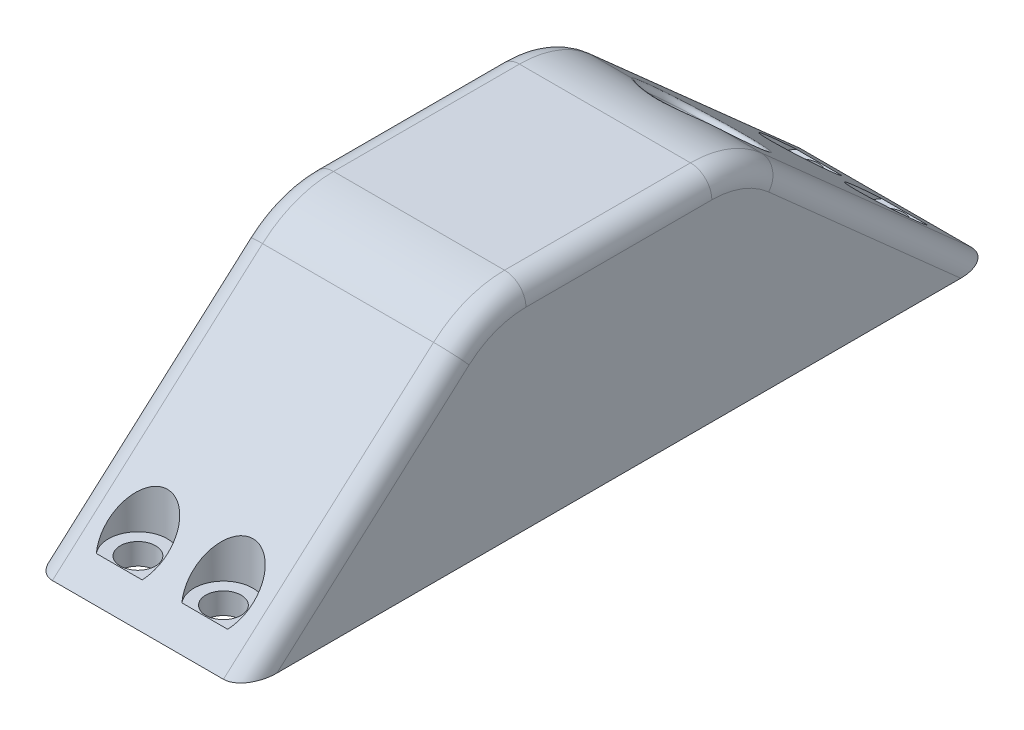
SolidWorks part; units mm, degrees
ref_plane "Front Plane" through (0, 0, 0) normal (0, 0, 1) x (1, 0, 0)
ref_plane "Top Plane" through (0, 0, 0) normal (0, 1, 0) x (1, 0, 0)
ref_plane "Right Plane" through (0, 0, 0) normal (1, 0, 0) x (0, 0, -1)
sketch "Sketch1" plane through (0, 0, 0) normal (0, 1, 0) x (1, 0, 0)
  line L0 (-14.05, 27.5) -> (14.05, 27.5)
  line L1 (-14.05, 27.5) -> (-14.05, -27.5)
  line L2 (14.05, 27.5) -> (14.05, -27.5)
  line L3 (-14.05, -27.5) -> (14.05, -27.5)
  line L4 (-14.05, 27.5) -> (14.05, -27.5) construction
  line L5 (14.05, 27.5) -> (-14.05, -27.5) construction
  point P1 (0, 0)
  dimension "D1" = 28.1
  dimension "D2" = 55
ref_plane "Plane1" through (0, 20, 0) normal (0, 1, 0) x (1, 0, 0)
sketch "Sketch2" plane through (0, 0, 0) normal (1, 0, 0) x (0, 0, -1)
  line L0 (-35, 0) -> (35, 0)
  line L1 (0, 0) -> (0, 20) construction
  line L2 (15.455, 20) -> (-15.455, 20) construction
  line L3 (-8.698, 20) -> (8.698, 20)
  line L4 (-35, 0) -> (-15.3416, 17.4741)
  line L5 (15.3416, 17.4741) -> (35, 0)
  arc A0 (8.698, 20) -> (15.3416, 17.4741) centre (8.698, 10) cw
  arc A1 (-8.698, 20) -> (-15.3416, 17.4741) centre (-8.698, 10) ccw
  point P4 (0, 0)
  point P12 (0, 20)
  point P14 (12.5, 20)
  point P17 (-12.5, 20)
  dimension "D3" = 10
  dimension "D1" = 70
  dimension "D2" = 25
extrude "Boss-Extrude1" add sketch "Sketch2" along normal blind 20
fillet "Fillet1" radius 2 10 edges at (20, 8.737, -25.1708) (20, 19.3472, -12.2518) (20, 8.737, 25.1708) (20, 19.3472, 12.2518) (20, 20, 0) (0, 8.737, -25.1708) (0, 19.3472, -12.2518) (0, 20, 0) (0, 19.3472, 12.2518) (0, 8.737, 25.1708)
ref_plane "Plane2" through (0, -17.3793, -19.5517) normal (0, -0.6644, -0.7474) x (-1, 0, 0)
sketch "Sketch3" plane through (0, -17.3793, -19.5517) normal (0, -0.6644, -0.7474) x (-1, 0, 0)
  line L0 (-18, 23.2527) -> (-2, 23.2527) construction
  line L1 (-17.05, 10.2527) -> (-2.95, 10.2527)
  line L2 (-17.05, 10.2527) -> (-17.05, -9.2473)
  line L3 (-17.05, -9.2473) -> (-2.95, -9.2473)
  line L4 (-2.95, 10.2527) -> (-2.95, -9.2473)
  line L5 (-20, -21.2527) -> (-20, 21.2527) construction
  line L7 (0, -21.2527) -> (0, 21.2527) construction
  dimension "D1" = 2.95
  dimension "D2" = 19.5
  dimension "D3" = 13
  dimension "D4" = 2.95
extrude "Cut-Extrude1" cut sketch "Sketch3" against normal blind 34 contours L2 L1 L4 L3
sketch "Sketch4" plane through (0, 7.663, -6.8115) normal (0, -0.7474, 0.6644) x (1, 0, 0)
  line L0 (2.95, 7.8407) -> (2.95, -11.5343) construction
  line L1 (2.95, 5.4657) -> (17.05, 5.4657)
  line L2 (2.95, 5.4657) -> (2.95, -11.5343)
  line L3 (2.95, -11.5343) -> (17.05, -11.5343)
  line L4 (17.05, 5.4657) -> (17.05, -11.5343)
  line L5 (17.05, 7.8407) -> (17.05, -11.5343) construction
  line L7 (10, 5.4657) -> (10, -11.5343) construction
  line L8 (2.95, -3.0343) -> (17.05, -3.0343) construction
  line L9 (2.95, -11.5343) -> (17.05, -11.5343) construction
  line L10 (2.95, -9.5343) -> (17.05, -9.5343)
  line L11 (2.95, -9.5343) -> (2.95, 3.4657)
  line L12 (2.95, 3.4657) -> (17.05, 3.4657)
  line L13 (17.05, -9.5343) -> (17.05, 3.4657)
  line L14 (2.95, -9.5343) -> (17.05, 3.4657) construction
  line L15 (2.95, 3.4657) -> (17.05, -9.5343) construction
  line L16 (4.05, -8.9343) -> (15.95, -8.9343)
  line L17 (4.05, -8.9343) -> (4.05, 2.8657)
  line L18 (4.05, 2.8657) -> (15.95, 2.8657)
  line L19 (15.95, -8.9343) -> (15.95, 2.8657)
  line L20 (4.05, -8.9343) -> (15.95, 2.8657) construction
  line L21 (4.05, 2.8657) -> (15.95, -8.9343) construction
  circle A0 centre (10, -3.0343) radius 4.75
  point P14 (10, -3.0343)
  point P19 (10, -3.0343)
  dimension "D6" = 9.5
  dimension "D1" = 17
  dimension "D3" = 13
  dimension "D4" = 11.8
  dimension "D5" = 11.9
extrude "Cut-Extrude2" cut sketch "Sketch4" against normal blind 20 contours A0 | A0 region at (10, 5.6471, -9.0794)
extrude "Cut-Extrude3" cut sketch "Sketch4<5>" against normal blind 11 contours L16 L19 L18 L17 A0 region at (4.2176, 5.6471, -9.0794)
sketch "Sketch4<5>" plane through (0, 7.663, -6.8115) normal (0, -0.7474, 0.6644) x (1, 0, 0) same geometry as "Sketch4"
extrude "Cut-Extrude4" cut sketch "Sketch4<6>" against normal blind 5.3 contours L12 L2 L10 L4 L19 L16 L17 L18 region at (10, 9.838, -4.3646)
sketch "Sketch4<6>" plane through (0, 7.663, -6.8115) normal (0, -0.7474, 0.6644) x (1, 0, 0) same geometry as "Sketch4"
extrude "Cut-Extrude5" cut sketch "Sketch4<8>" against normal blind 2 contours L1 L4 L3 L2
sketch "Sketch4<8>" plane through (0, 7.663, -6.8115) normal (0, -0.7474, 0.6644) x (1, 0, 0) same geometry as "Sketch4"
fillet "Fillet2" radius 0.5 2 edges at (10, 12.2077, -21.2664) (10.7874, 18.3901, -14.1392)
ref_plane "Plane3" through (0, 10, 0) normal (0, 1, 0) x (1, 0, 0)
sketch "Sketch7" plane through (0, 10, 0) normal (0, 1, 0) x (1, 0, 0)
  line L0 (18, 35) -> (2, 35) construction
  line L1 (18, 15.3416) -> (18, 35) construction
  line L2 (10, 35) -> (10, -35) construction
  line L3 (18, -35) -> (2, -35) construction
  line L4 (10, 0) -> (20, 0) construction
  line L5 (20, 8.698) -> (20, -8.698) construction
  circle A0 centre (14, 31) radius 1.65
  circle A1 centre (6, 31) radius 1.65
  circle A2 centre (14, -31) radius 1.65
  circle A3 centre (6, -31) radius 1.65
  circle A4 centre (14, 31) radius 2.765
  circle A5 centre (6, 31) radius 2.765
  circle A6 centre (6, -31) radius 2.765
  circle A7 centre (14, -31) radius 2.765
  dimension "D1" = 3.3
  dimension "D2" = 4
  dimension "D3" = 4
  dimension "D4" = 5.53
  dimension "D5" = 2
  dimension "D6" = 2
extrude "Cut-Extrude7" cut sketch "Sketch7" against normal blind 15 contours A3 | A2 | A1 | A0 region at (14, 10, -31) region at (6, 10, -31) region at (14, 10, 31) region at (6, 10, 31)
extrude "Cut-Extrude8" cut sketch "Sketch7<3>" against normal blind 8 contours A4 A0 | A6 A3 | A7 A2 | A5 region at (11.3132, 10, -31) region at (3.3132, 10, 31) region at (11.3132, 10, 31)
sketch "Sketch7<3>" plane through (0, 10, 0) normal (0, 1, 0) x (1, 0, 0) same geometry as "Sketch7"
